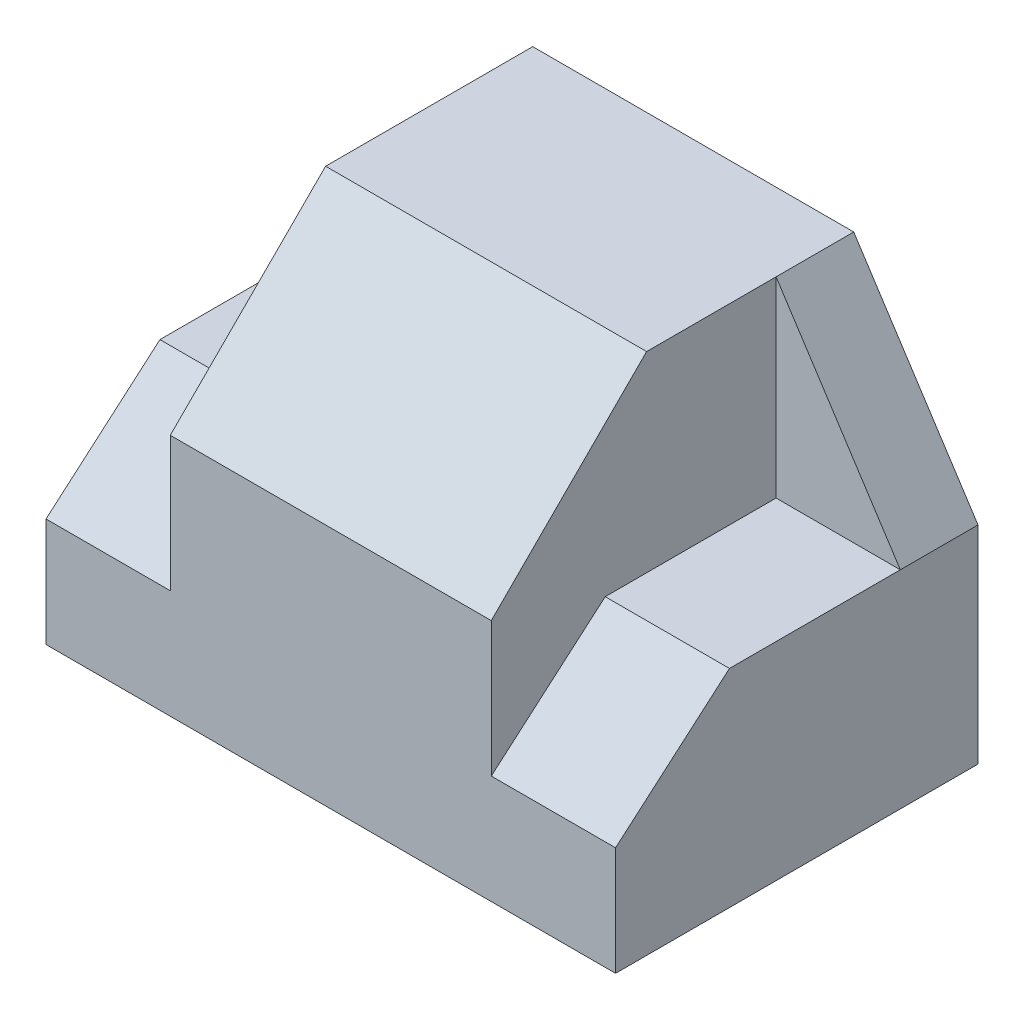
SolidWorks part; units mm, degrees
ref_plane "정면" through (0, 0, 0) normal (0, 0, 1) x (1, 0, 0)
ref_plane "윗면" through (0, 0, 0) normal (0, 1, 0) x (1, 0, 0)
ref_plane "우측면" through (0, 0, 0) normal (1, 0, 0) x (0, 0, -1)
sketch "스케치4" plane through (0, 0, 0) normal (0, 0, 1) x (1, 0, 0)
  line L0 (0, 0) -> (0, 104.3876) construction
  line L1 (-55, 0) -> (55, 0)
  line L2 (55, 0) -> (55, 21)
  line L3 (-55, 0) -> (-55, 21)
  line L4 (55, 21) -> (31, 21)
  line L5 (-55, 21) -> (-31, 21)
  line L6 (31, 21) -> (31, 47)
  line L7 (-31, 21) -> (-31, 47)
  line L8 (31, 47) -> (-31, 47)
  line L9 (55, 21) -> (55, 40)
  line L10 (-55, 21) -> (-55, 40)
  line L11 (55, 40) -> (31, 40)
  line L12 (-55, 40) -> (-31, 40)
  line L13 (31, 47) -> (31, 77)
  line L14 (-31, 47) -> (-31, 77)
  line L15 (31, 77) -> (-31, 77)
  line L16 (55, 40) -> (31, 77)
  line L17 (-55, 40) -> (-31, 77)
  line L18 (99.8483, 140.4422) -> (56.2781, 133.6129)
  point P12 (0, 47)
  point P18 (0, 77)
  dimension "D1" = 110
  dimension "D2" = 21
  dimension "D3" = 24
  dimension "D4" = 26
  dimension "D5" = 19
  dimension "D6" = 30
extrude "보스-돌출4" add sketch "스케치4" along normal blind 70 contours L1 L0 L8 L7 L5 L3 | L0 L1 L2 L4 L6 L8 region at (-22.5678, 20.1588, 0) region at (22.5678, 20.1588, 0)
extrude "보스-돌출5" add sketch "스케치4<3>" along normal blind 48 contours L9 L11 L6 L4 | L12 L10 L5 L7 region at (-43, 30.5, 0) region at (43, 30.5, 0)
sketch "스케치4<3>" plane through (0, 0, 0) normal (0, 0, 1) x (1, 0, 0) same geometry as "스케치4"
extrude "보스-돌출6" add sketch "스케치4<4>" along normal blind 40 contours L8 L0 L15 L14 | L0 L8 L13 L15 region at (-15.5, 62, 0) region at (15.5, 62, 0)
sketch "스케치4<4>" plane through (0, 0, 0) normal (0, 0, 1) x (1, 0, 0) same geometry as "스케치4"
extrude "보스-돌출7" add sketch "스케치4<5>" along normal blind 15 contours L11 L16 L13 L6 | L17 L12 L7 L14 region at (-39, 52.3333, 0) region at (39, 52.3333, 0)
sketch "스케치4<5>" plane through (0, 0, 0) normal (0, 0, 1) x (1, 0, 0) same geometry as "스케치4"
ref_plane "평면1" through (55, 21, 70) normal (0, 1, 0) x (1, 0, 0)
sketch "스케치6" plane through (31, 0, 0) normal (1, 0, 0) x (0, 0, -1)
  line L0 (-40, 77) -> (-70, 47)
  line L1 (-48, 40) -> (-70, 21)
  line L2 (-64.225, 21) -> (-75.775, 21) construction
  line L3 (-70, 0) -> (-70, 21) construction
  line L4 (-70, 21) -> (-48, 21)
  line L5 (-48, 21) -> (-48, 40)
  line M4 (-40, 77) -> (-40, 47)
  line M5 (-40, 47) -> (-70, 47)
  line M7 (-70, 21) -> (-48, 21)
  line M8 (-48, 21) -> (-48, 40)
extrude "보스-돌출8" add sketch "스케치6" against normal blind 62 contours L0 M4 M5 region at (31, 57, 50)
extrude "보스-돌출9" add sketch "스케치6<3>" along normal up to vertex (24 mm away) contours L1 M8 M7 region at (31, 27.3333, 55.3333) up to point (55, 21, 70)
sketch "스케치6<3>" plane through (31, 0, 0) normal (1, 0, 0) x (0, 0, -1) same geometry as "스케치6"
sketch "스케치8" plane through (0, 46.6556, 40.2935) normal (0, 0.7568, 0.6536) x (1, 0, 0)
extrude "보스-돌출10" add sketch "스케치6<4>" against normal blind 86 contours L1 L4 L5
sketch "스케치6<4>" plane through (31, 0, 0) normal (1, 0, 0) x (0, 0, -1) same geometry as "스케치6"
